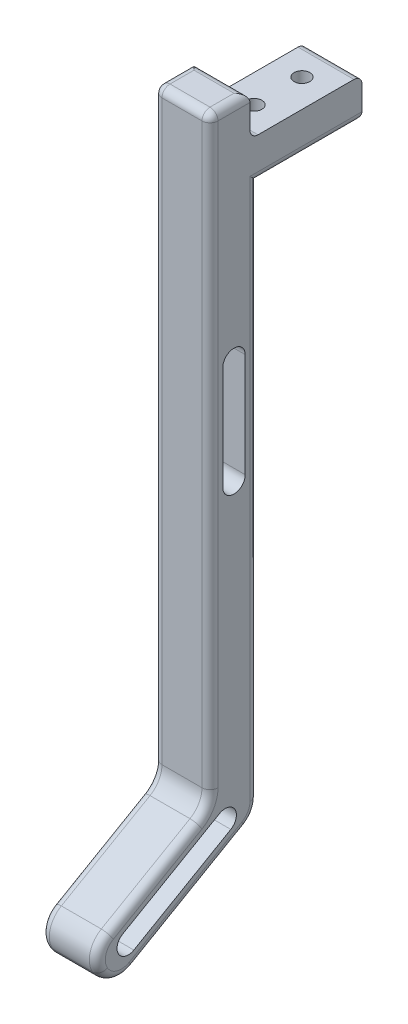
SolidWorks part; units mm, degrees
ref_plane "Front Plane" through (0, 0, 0) normal (0, 0, 1) x (1, 0, 0)
ref_plane "Top Plane" through (0, 0, 0) normal (0, 1, 0) x (1, 0, 0)
ref_plane "Right Plane" through (0, 0, 0) normal (1, 0, 0) x (0, 0, -1)
sketch "Sketch1" plane through (0, 0, 0) normal (1, 0, 0) x (0, 0, -1)
  line L1 (-2.3155, -8.0332) -> (20.7814, 5.3018)
  line L2 (13.1614, 9.7012) -> (-6.1255, -1.4341)
  line L3 (20.7814, 92.1698) -> (37.2914, 92.1698)
  line L4 (19.5114, 104.8698) -> (19.5114, 98.5198)
  line L5 (-2.3155, -8.0332) -> (-6.1255, -1.4341)
  line L6 (13.1614, 9.7012) -> (13.1614, 104.8698)
  line L7 (13.1614, 104.8698) -> (19.5114, 104.8698)
  line L8 (19.5114, 98.5198) -> (37.2914, 98.5198)
  line L9 (37.2914, 98.5198) -> (37.2914, 92.1698)
  line L10 (20.7814, 92.1698) -> (20.7814, 5.3018)
  dimension "D1" = 99.568
  dimension "D2" = 120
  dimension "D3" = 26.67
  dimension "D4" = 7.62
  dimension "D5" = 12.7
  dimension "D6" = 16.51
  dimension "D7" = 6.35
  dimension "D8" = 6.35
  dimension "D9" = 7.62
extrude "Boss-Extrude1" add sketch "Sketch1" along normal blind 8.89
sketch "Sketch2" plane through (8.89, 0, 0) normal (1, 0, 0) x (0, 0, -1)
  line L0 (1.0679, -3.7334) -> (16.4658, 5.1566)
  line L2 (14.6878, 8.2361) -> (-0.7101, -0.6539)
  line L3 (13.1614, 9.7012) -> (-6.1255, -1.4341) construction
  line L4 (1.0679, -3.7334) -> (4.3239, -1.7333)
  line L5 (-6.1255, -1.4341) -> (-2.3155, -8.0332) construction
  arc A0 (14.6878, 8.2361) -> (16.4658, 5.1566) centre (15.5768, 6.6964) cw
  arc A1 (1.0679, -3.7334) -> (-0.7101, -0.6539) centre (0.1789, -2.1936) cw
  dimension "D1" = 3.81
  dimension "D2" = 5.08
  dimension "D3" = 3.556
  dimension "D4" = 0
  dimension "D6" = 17.78
extrude "Cut-Extrude1" cut sketch "Sketch2" against normal blind 10.16 contours A1 L0 A0 L2 region at (8.89, 2.2514, -7.8778)
sketch "Sketch3" plane through (8.89, 0, 0) normal (1, 0, 0) x (0, 0, -1)
  line L1 (19.5114, 104.8698) -> (13.1614, 104.8698) construction
  line L2 (15.1934, 69.3098) -> (15.1934, 52.7998)
  line L3 (20.7814, 5.3018) -> (20.7814, 92.1698) construction
  line L4 (18.7494, 69.3098) -> (18.7494, 52.7998)
  arc A0 (18.7494, 69.3098) -> (15.1934, 69.3098) centre (16.9714, 69.3098) ccw
  arc A1 (18.7494, 52.7998) -> (15.1934, 52.7998) centre (16.9714, 52.7998) cw
  dimension "D1" = 3.556
  dimension "D2" = 16.51
  dimension "D3" = 3.81
  dimension "D4" = 35.56
extrude "Cut-Extrude2" cut sketch "Sketch3" against normal blind 10.16
hole_wizard "Tap Drill for M3 Tap1" positions "Sketch5" profile "Sketch4" hole size "M3" standard "ISO" end condition through all
sketch "Sketch5" plane through (0, 98.5198, 0) normal (0, 1, 0) x (1, 0, 0)
  line L0 (8.89, 37.2914) -> (0, 37.2914) construction
  line L1 (0, 37.2914) -> (0, 19.5114) construction
  point P0 (4.445, 32.2114)
  point P2 (4.445, 24.5914)
  dimension "D1" = 5.08
  dimension "D2" = 4.445
  dimension "D3" = 7.62
sketch "Sketch4" plane through (4.445, 98.5198, -32.2114) normal (1, 0, 0) x (0, 0, 1)
  line L0 (0, 0) -> (0, 106.553)
  line L1 (0, 106.553) -> (1.25, 106.553)
  line L2 (1.25, 106.553) -> (1.25, 0)
  line L5 (1.25, 0) -> (0, 0)
  line L11 (0, -6.35) -> (0, 107.95) construction
  dimension "Thru Hole Dia." = 2.5
  dimension "Thru Hole Depth" = 106.553
fillet "Fillet5" radius 1.27 2 edges at (4.445, 98.5198, -37.2914) (4.445, 98.5198, -19.5114)
fillet "Fillet6" radius 3.81 4 edges at (4.445, 9.7012, -13.1614) (4.445, 5.3018, -20.7814) (4.445, -8.0332, 2.3155) (4.445, -1.4341, 6.1255)
fillet "Fillet7" radius 1.27 23 edges at (0, 49.8356, -20.7814) (0, 5.5965, -20.2709) (0, -0.9631, -9.9302) (0, -6.5088, 1.9071) (0, -1.8425, 4.6012) (0, 4.5361, -4.2152) (0, 9.9959, -12.6509) (8.89, 49.8356, -20.7814) (8.89, 5.5965, -20.2709) (8.89, -0.9631, -9.9302) (8.89, -6.5088, 1.9071) (8.89, -1.8425, 4.6012) (8.89, 4.5361, -4.2152) (8.89, 9.9959, -12.6509) (4.445, 104.8698, -19.5114) (8.89, 104.8698, -16.3364) (4.445, 104.8698, -13.1614) (0, 104.8698, -16.3364) (4.445, 92.1698, -37.2914) (8.89, 92.1698, -29.0364) (0, 92.1698, -29.0364) (0, 58.3854, -13.1614) (8.89, 58.3854, -13.1614)
